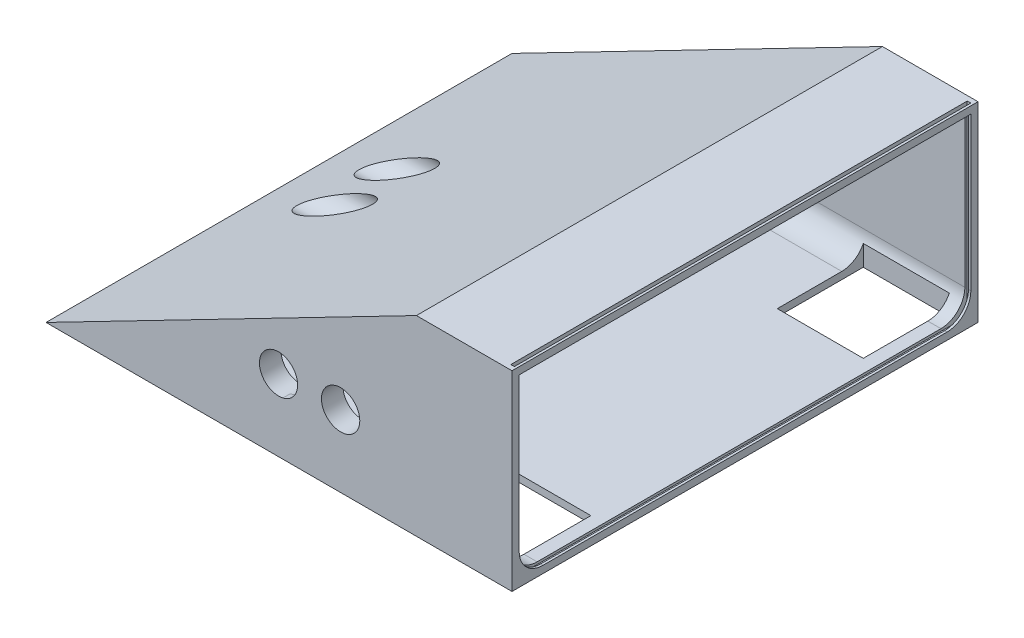
SolidWorks part; units mm, degrees
ref_plane "Front Plane" through (0, 0, 0) normal (0, 0, 1) x (1, 0, 0)
ref_plane "Top Plane" through (0, 0, 0) normal (0, 1, 0) x (1, 0, 0)
ref_plane "Right Plane" through (0, 0, 0) normal (1, 0, 0) x (0, 0, -1)
ref_plane "Plane1" through (0, 0, 0) normal (1, 0, 0) x (0, 0, -1)
ref_plane "Plane2" through (0, 0, 97.5) normal (0, 0, 1) x (1, 0, 0)
ref_plane "Plane3" through (1, 0, 0) normal (1, 0, 0) x (0, 0, -1)
sketch "Sketch2" plane through (0, 0, 0) normal (0, 0, 1) x (1, 0, 0)
  line L0 (0, 0) -> (195, 0)
  line L1 (195, 0) -> (195, 80)
  line L2 (195, 80) -> (155, 80)
  line L3 (155, 80) -> (0, 0)
  dimension "D1" = 195
  dimension "D2" = 40
  dimension "80" = 80
extrude "Robot" add sketch "Sketch2" along normal blind 195
sketch "Sketch3" plane through (0, 0, 195) normal (0, 0, 1) x (1, 0, 0)
  line L0 (0, 0) -> (195, 0) construction
  circle A0 centre (97.2899, 30) radius 8.02
  circle A1 centre (123.2899, 30) radius 8.02
  dimension "D1" = 30
  dimension "D2" = 16.04
  dimension "D4" = 16.04
  dimension "D3" = 26
  dimension "D5" = 30
sketch "Arriba" plane through (0, 80, 0) normal (0, 1, 0) x (1, 0, 0)
  line L0 (195, 0) -> (195, -195) construction
  line L1 (0, 0) -> (0, -195) construction
  line L2 (0, -97.5) -> (195, -97.5) construction
  line L3 (0, 0) -> (195, 0) construction
  line L4 (0, -195) -> (195, -195) construction
  line L5 (97.5, 0) -> (97.5, -195) construction
sketch "Adelante" plane through (0, 0, 0) normal (1, 0, 0) x (0, 0, -1)
  line L0 (0, 80) -> (0, 0) construction
  line L1 (-97.5, 80) -> (-97.5, 0) construction
  line L2 (0, 80) -> (-195, 80) construction
  line L3 (-195, 0) -> (0, 0) construction
  line L4 (-195, 80) -> (-195, 0) construction
  line L5 (0, 0) -> (-195, 0) construction
sketch "Sketch9" plane through (0, 0, 0) normal (0, 0, -1) x (-1, 0, 0)
  line L1 (0, 0) -> (-195, 0) construction
  circle A0 centre (-97.284, 30) radius 8.2
  circle A1 centre (-123.284, 30) radius 8.2
  dimension "D2" = 16.4
  dimension "D4" = 30
  dimension "D6" = 16.4
  dimension "D3" = 30
  dimension "D5" = 26
sketch "Sketch10" plane through (0, 0, 0) normal (0, -1, 0) x (-1, 0, 0)
  line L0 (0, -195) -> (-195, -195) construction
  line L1 (-187, -191) -> (-150, -191)
  line L2 (-187, -191) -> (-187, -154)
  line L3 (-187, -154) -> (-150, -154)
  line L4 (-150, -191) -> (-150, -154)
  line L5 (-195, 0) -> (-195, -195) construction
  dimension "D1" = 4
  dimension "D2" = 8
  dimension "D3" = 37
  dimension "D4" = 37
sketch "Sketch12" plane through (0, 0, 0) normal (0, -1, 0) x (-1, 0, 0)
  line L0 (-195, 0) -> (-195, -195) construction
  line L1 (-187, -40) -> (-151, -40)
  line L2 (-187, -40) -> (-187, -4)
  line L3 (-187, -4) -> (-151, -4)
  line L4 (-151, -40) -> (-151, -4)
  line L5 (0, 0) -> (-195, 0) construction
  dimension "D1" = 8
  dimension "D2" = 4
  dimension "D3" = 36
  dimension "D4" = 36
sketch "Sketch13" plane through (0, 0, 0) normal (0, -1, 0) x (1, 0, 0)
  line L0 (0, 0) -> (195, 0) construction
  line L1 (15, 8) -> (22.1, 8)
  line L2 (15, 8) -> (15, 15.1)
  line L3 (15, 15.1) -> (22.1, 15.1)
  line L4 (22.1, 8) -> (22.1, 15.1)
  line L5 (0, 0) -> (0, 195) construction
  dimension "D1" = 8
  dimension "D2" = 15
  dimension "D3" = 7.1
  dimension "D4" = 7.1
sketch "Sketch14" plane through (0, 0, 0) normal (0, -1, 0) x (-1, 0, 0)
  line L0 (0, -195) -> (-195, -195) construction
  line L1 (-15, -179.9) -> (-22.1, -179.9)
  line L2 (-15, -179.9) -> (-15, -187)
  line L3 (-15, -187) -> (-22.1, -187)
  line L4 (-22.1, -179.9) -> (-22.1, -187)
  line L5 (0, 0) -> (0, -195) construction
  dimension "D1" = 8
  dimension "D2" = 15
  dimension "D3" = 7.1
  dimension "D4" = 7.1
sketch "Sketch15" plane through (0, 0, 0) normal (0, -1, 0) x (-1, 0, 0)
  line L0 (0, -97.5) -> (-195, -97.5) construction
  line L1 (-15, -93.95) -> (-22.1, -93.95)
  line L2 (-15, -93.95) -> (-15, -101.05)
  line L3 (-15, -101.05) -> (-22.1, -101.05)
  line L4 (-22.1, -93.95) -> (-22.1, -101.05)
  line L5 (0, 0) -> (0, -195) construction
  dimension "D1" = 3.55
  dimension "D2" = 3.55
  dimension "D3" = 7.1
  dimension "D4" = 15
shell "Vacio por dentro 3mm" thickness 3 removed face at (195, 40, 97.5)
extrude "Ultrasonico Derecha" cut sketch "Sketch3" against normal blind 3
sketch "Ultrasonico Centro " plane through (0, 0, 0) normal (1, 0, 0) x (0, 0, -1)
  line L0 (0, 0) -> (-195, 0) construction
  line L1 (-97.5, 80) -> (-97.5, 0) construction
  circle A0 centre (-85, 19) radius 8.7
  circle A1 centre (-111, 19) radius 8.7
  dimension "D2" = 17.4
  dimension "D4" = 17.4
  dimension "D1" = 19
  dimension "D3" = 12.5
  dimension "D5" = 13.5
  dimension "D6" = 19
extrude "Ultrasonico Izquierda" cut sketch "Sketch9" against normal blind 3
extrude "Rueda Derecha" cut sketch "Sketch10" against normal blind 3
extrude "Rueda Izquierda" cut sketch "Sketch12" against normal blind 3
extrude "Cyn70 Derecha" cut sketch "Sketch14" against normal blind 4
extrude "Cny70 Centro" cut sketch "Sketch15" against normal blind 4
extrude "Cny70 Izquierda" cut sketch "Sketch13" against normal blind 4
extrude "Cut-Extrude4" cut sketch "Ultrasonico Centro " along normal blind 75
fillet "Fillet2" radius 10 2 edges at (103.6768, 3, 3) (103.6768, 3, 192)
sketch "Sketch16" plane through (0, 0, 195) normal (0, 0, 1) x (1, 0, 0)
  circle A0 centre (123.2899, 30) radius 8.02
  circle A1 centre (123.2899, 30) radius 8.6857
  circle A2 centre (97.3351, 30.0107) radius 8.6857
  circle A3 centre (97.3351, 30.0107) radius 8.02
extrude "Boss-Extrude1" add sketch "Sketch16" against normal blind 9
mirror "Mirror1" about plane through (0, 0, 97.5) normal (0, 0, 1) of "Boss-Extrude1"
sketch "Sketch18" plane through (1, 0, 0) normal (1, 0, 0) x (0, 0, -1)
  circle A0 centre (-85, 19) radius 8.7
  circle A1 centre (-85, 19) radius 8.2
  circle A2 centre (-111, 19) radius 8.7192
  circle A3 centre (-111, 19) radius 8.2
  dimension "D1" = 17.4
  dimension "D2" = 16.4
  dimension "D3" = 16.4
  dimension "D4" = 17.4384
extrude "Boss-Extrude2" add sketch "Sketch18" along normal blind 60
ref_plane "Plane4" through (0, 0, 0) normal (-0.4586, 0.8886, 0) x (0.8886, 0.4586, 0)
sketch "Sketch23" plane through (0, 0, 0) normal (-0.4586, 0.8886, 0) x (0.8886, 0.4586, 0)
  line L1 (0, -64.3188) -> (76.5925, -64.3188)
  line L2 (0, -64.3188) -> (0, -130.2867)
  line L3 (0, -130.2867) -> (76.5925, -130.2867)
  line L4 (76.5925, -64.3188) -> (76.5925, -130.2867)
extrude "Cut-Extrude5" cut sketch "Sketch23" along normal blind 25
sketch "Sketch24" plane through (0, 80, 0) normal (0, 1, 0) x (1, 0, 0)
  line L0 (195, 0) -> (155, 0) construction
  line L1 (192.5, -2) -> (194, -2)
  line L2 (192.5, -2) -> (192.5, -193)
  line L3 (192.5, -193) -> (194, -193)
  line L4 (194, -2) -> (194, -193)
  line L5 (195, -195) -> (155, -195) construction
  line L6 (195, -195) -> (195, 0) construction
  dimension "D1" = 2
  dimension "D2" = 2
  dimension "D3" = 1.5
  dimension "D4" = 1
extrude "Cut-Extrude6" cut sketch "Sketch24" against normal blind 78
ref_plane "Plane5" through (0, 3, 0) normal (0, -1, 0) x (-1, 0, 0)
